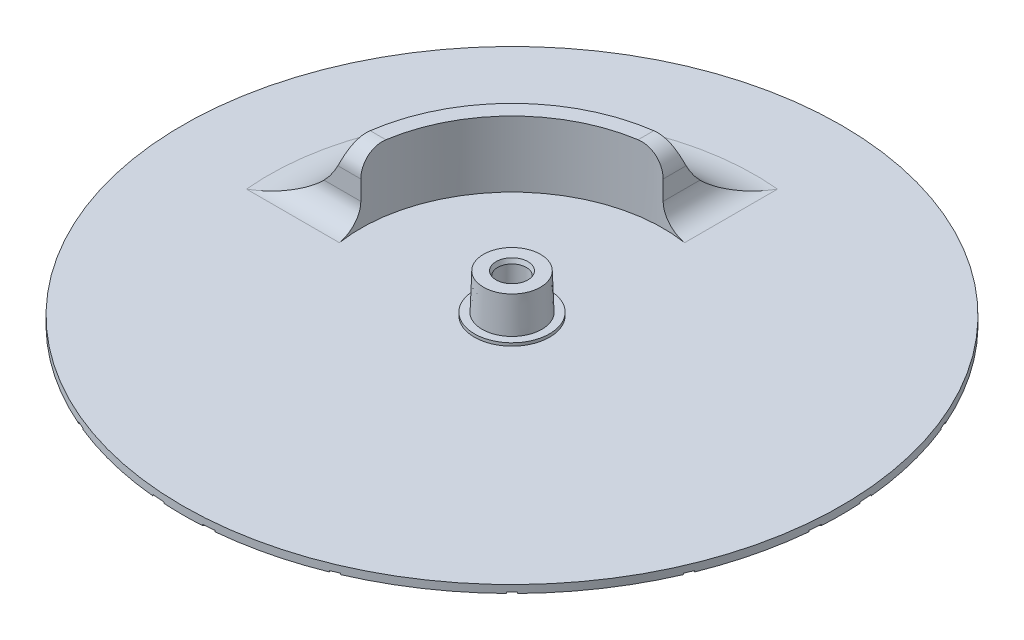
SolidWorks part; units mm, degrees
ref_plane "Front Plane" through (0, 0, 0) normal (0, 0, 1) x (1, 0, 0)
ref_plane "Top Plane" through (0, 0, 0) normal (0, 1, 0) x (1, 0, 0)
ref_plane "Right Plane" through (0, 0, 0) normal (1, 0, 0) x (0, 0, -1)
sketch "Sketch1" plane through (0, 0, 0) normal (0, 1, 0) x (1, 0, 0)
  circle A0 centre (0, 0) radius 21.5
  circle A1 centre (0, 0) radius 2.15
  dimension "D1" = 43
extrude "Boss-Extrude1" add sketch "Sketch1" along normal blind 1
sketch "Sketch2" plane through (0, 1, 0) normal (0, 1, 0) x (1, 0, 0)
  line L0 (0, 19.5) -> (0, 21.5)
  line L1 (-19.5, 0) -> (-21.5, 0)
  arc A0 (0, 21.5) -> (-21.5, 0) centre (0, 0) ccw
  arc A1 (0, 19.5) -> (-19.5, 0) centre (0, 0) ccw
  circle A2 centre (0, 0) radius 21.5 construction
  dimension "D1" = 2
extrude "Boss-Extrude2" add sketch "Sketch2" along normal blind 8.5
sketch "Sketch3" plane through (0, 1, 0) normal (0, 1, 0) x (1, 0, 0)
  circle A0 centre (0, 0) radius 3.85
  dimension "D1" = 7.7
extrude "Boss-Extrude3" add sketch "Sketch3" along normal blind 5
chamfer "Chamfer1" distance 5 angle 2 1 edges at (0, 6, 3.85) first distance on face at (0, 6, 3.85)
sketch "Sketch4" plane through (0, 6, 0) normal (0, 1, 0) x (1, 0, 0)
  circle A0 centre (0, 0) radius 1.85
  dimension "D1" = 3.7
extrude "Cut-Extrude1" cut sketch "Sketch4" against normal blind 9
chamfer "Chamfer2" distance 0.2 angle 70 1 edges at (0, 6, 1.85) first distance on face at (0, 6, 1.85)
sketch "Sketch5" plane through (0, 1, 0) normal (0, 1, 0) x (1, 0, 0)
  circle A0 centre (0, 0) radius 3.85
  circle A1 centre (0, 0) radius 4.85
  dimension "D1" = 1
extrude "Boss-Extrude4" add sketch "Sketch5" along normal blind 0.38
fillet "Fillet1" radius 3 4 edges at (-20.5, 9.5, 0) (-20.5, 1, 0) (0, 9.5, -20.5) (0, 1, -20.5)
sketch "Sketch6" plane through (0, 1, 0) normal (0, 1, 0) x (1, 0, 0)
  circle A0 centre (0, 0) radius 42.5
  circle A1 centre (0, 0) radius 2.15
  dimension "D1" = 85
extrude "Boss-Extrude6" add sketch "Sketch6" against normal up to surface (1 mm away) up to face at (0, 0, 21.5)
sketch "Sketch8" plane through (0, 0, 0) normal (0, -1, 0) x (1, 0, 0)
  line L0 (0, 0) -> (-37.1856, 37.1856) construction
  line L1 (0, 0) -> (-58.8083, 0) construction
  line L2 (62.9923, -63.6994) -> (-63.6994, 62.9923)
  line L3 (62.9923, -63.6994) -> (63.6994, -62.9923)
  line L4 (-63.6994, 62.9923) -> (-62.9923, 63.6994)
  line L5 (63.6994, -62.9923) -> (-62.9923, 63.6994)
  line L6 (62.9923, -63.6994) -> (-62.9923, 63.6994) construction
  line L7 (-63.6994, 62.9923) -> (63.6994, -62.9923) construction
  line L8 (85.7999, -63.6994) -> (-40.8919, 62.9923)
  line L9 (85.7999, -63.6994) -> (86.507, -62.9923)
  line L10 (86.507, -62.9923) -> (-40.1848, 63.6994)
  line L11 (-40.8919, 62.9923) -> (-40.1848, 63.6994)
  line L12 (108.6074, -63.6994) -> (-18.0844, 62.9923)
  line L13 (108.6074, -63.6994) -> (109.3145, -62.9923)
  line L14 (109.3145, -62.9923) -> (-17.3773, 63.6994)
  line L15 (-18.0844, 62.9923) -> (-17.3773, 63.6994)
  line L28 (40.1848, -63.6994) -> (-86.507, 62.9923)
  line L29 (40.1848, -63.6994) -> (40.8919, -62.9923)
  line L30 (40.8919, -62.9923) -> (-85.7999, 63.6994)
  line L31 (-86.507, 62.9923) -> (-85.7999, 63.6994)
  line L32 (17.3773, -63.6994) -> (-109.3145, 62.9923)
  line L33 (17.3773, -63.6994) -> (18.0844, -62.9923)
  line L34 (18.0844, -62.9923) -> (-108.6074, 63.6994)
  line L35 (-109.3145, 62.9923) -> (-108.6074, 63.6994)
  line L40 (40.1848, -63.6994) -> (17.3773, -63.6994) construction
  line L42 (109.3145, -62.9923) -> (86.507, -62.9923) construction
  point P2 (-63.3459, 63.3459)
  dimension "D1" = 45
  dimension "D2" = 1
  dimension "D3" = 3
  dimension "D4" = 3
extrude "Cut-Extrude2" cut sketch "Sketch8" against normal blind 0.16
pattern_circular "CirPattern1" count 2 every 90 about axis through (0, 6, 0) along (0, -1, 0) of "Cut-Extrude2"
fillet "Fillet2" radius 10 1 edges at (-15.2028, 1, -15.2028)
sketch "Sketch9" plane through (0, 1, 0) normal (0, -1, 0) x (1, 0, 0)
  circle A0 centre (0, 0) radius 1.85
  circle A1 centre (0, 0) radius 2.15
extrude "Boss-Extrude7" add sketch "Sketch9" along normal up to surface (1 mm away) up to face at (0, 0, 9.778)
equation "\"D3@Sketch8\"=\"D4@Sketch8\""
